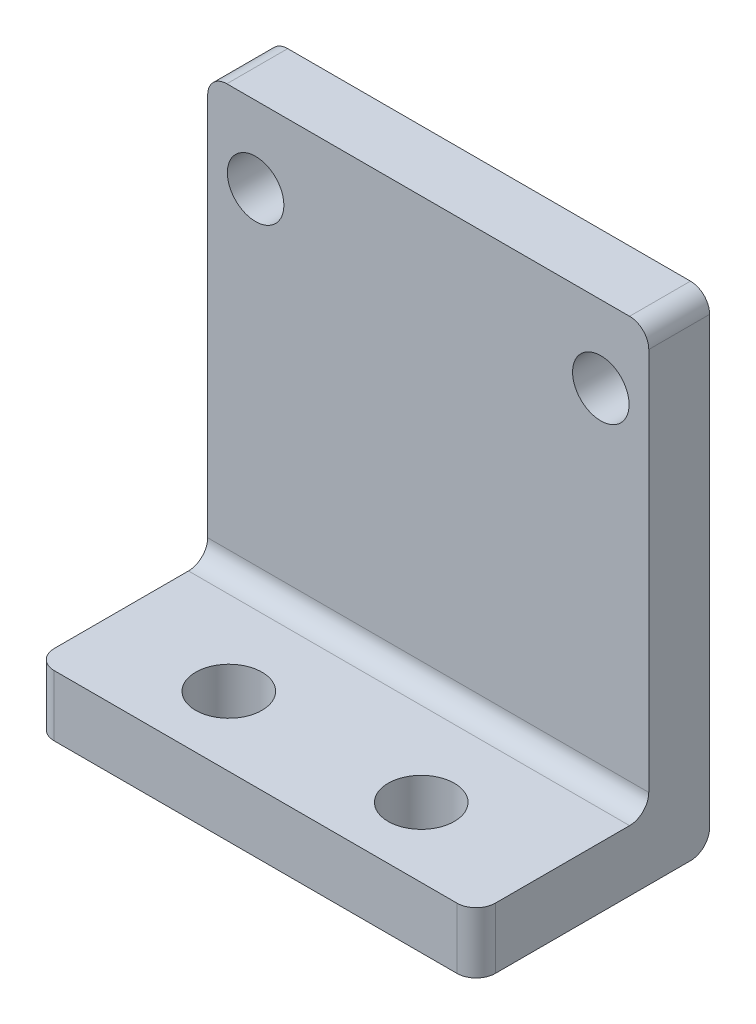
SolidWorks part; units mm, degrees
ref_plane "Front Plane" through (0, 0, 0) normal (0, 0, 1) x (1, 0, 0)
ref_plane "Top Plane" through (0, 0, 0) normal (0, 1, 0) x (1, 0, 0)
ref_plane "Right Plane" through (0, 0, 0) normal (1, 0, 0) x (0, 0, -1)
sketch "Sketch1" plane through (0, 0, 0) normal (0, 0, 1) x (1, 0, 0)
  line L0 (0, -20) -> (23, -20)
  line L1 (0, 0) -> (23, 0)
  line L2 (0, 0) -> (0, -23.175)
  line L3 (0, -23.175) -> (23, -23.175)
  line L4 (23, 0) -> (23, -23.175)
  line L5 (0, 0) -> (0, 2)
  line L6 (0, 2) -> (23, 2)
  line L7 (23, 2) -> (23, 0)
  circle A0 centre (2.5, -2) radius 1.4732
  circle A1 centre (20.5, -2) radius 1.4732
  dimension "D2" = 2.9464
  dimension "D1" = 18
  dimension "D4" = 3.175
  dimension "D5" = 23
  dimension "D6" = 2.5
  dimension "D7" = 2
  dimension "D3" = 20
  dimension "D8" = 2
extrude "Boss-Extrude1" add sketch "Sketch1" along normal blind 3.175 contours L4 L1 L2 L0 A1 A0 | L4 L0 L2 L3 | L7 L6 L5 L1 region at (11.5, -10.2444, 0) region at (11.5, -21.5875, 0) region at (11.5, 1, 0)
extrude "Boss-Extrude2" add sketch "Sketch1<3>" along normal blind 9 from surface contours L4 L0 L2 L3 region at (11.5, -21.5875, 0) starting at face at (21.9732, -2, 3.175)
sketch "Sketch1<3>" plane through (0, 0, 0) normal (0, 0, 1) x (1, 0, 0) same geometry as "Sketch1"
sketch "Mount Hole Location" plane through (0, -20, 0) normal (0, 1, 0) x (1, 0, 0)
  line L0 (0, -12.175) -> (23, -12.175) construction
  line L1 (8.579, -8.5555) -> (14.421, -8.5555) construction
  line L3 (0, -4.809) -> (23, -4.809) construction
  line L4 (0, -12.175) -> (0, -3.175) construction
  line L5 (23, -12.175) -> (23, -3.175) construction
  line L6 (23, -12.175) -> (0, -12.175) construction
  line L7 (6.4835, -6.46) -> (6.4835, -4.809) construction
  circle A0 centre (16.5165, -8.5555) radius 3.4925 construction
  circle A1 centre (16.5165, -8.5555) radius 2.0955
  circle A2 centre (6.4835, -8.5555) radius 2.0955
  circle A3 centre (6.4835, -8.5555) radius 3.4925 construction
  point P0 (11.5, -8.5555)
  point P4 (11.5, -12.175)
  point P15 (11.5, -8.5555)
  dimension "D2" = 6.985
  dimension "D3" = 4.191
  dimension "D1" = 1.651
  dimension "D4" = 5.842
  dimension "D5" = 7.366
hole_wizard "#8-32 Tapped Hole1" positions "3DSketch1" profile "Sketch3" tap size "#8-32" standard "ANSI Inch" end condition through all
sketch3d "3DSketch1"
  point P5 (6.4835, -20, 8.5555)
  point P8 (16.5165, -20, 8.5555)
sketch "Sketch3" plane through (6.4835, -20, 8.5555) normal (1, 0, 0) x (0, 0, 1)
  line L0 (0, 0) -> (0, 3.175)
  line L1 (0, 3.175) -> (1.7272, 3.175)
  line L2 (1.7272, 3.175) -> (1.7272, 0)
  line L5 (1.7272, 0) -> (0, 0)
  line L11 (0, -6.35) -> (0, 107.95) construction
  dimension "Thru Tap Drill Dia." = 3.4544
  dimension "Thru Tap Drill Depth" = 3.175
cosmetic thread "Hole Thread1" parameters "D2"=4.1656
cosmetic thread "Hole Thread2" parameters "D2"=4.1656
fillet "Fillet1" radius 1 6 edges at (0, -21.5875, 12.175) (23, -21.5875, 12.175) (11.5, -23.175, 0) (11.5, -20, 3.175) (23, 2, 1.5875) (0, 2, 1.5875)
equation "\"D6@Sketch1\"=(\"D5@Sketch1\"-\"D1@Sketch1\")/2"
